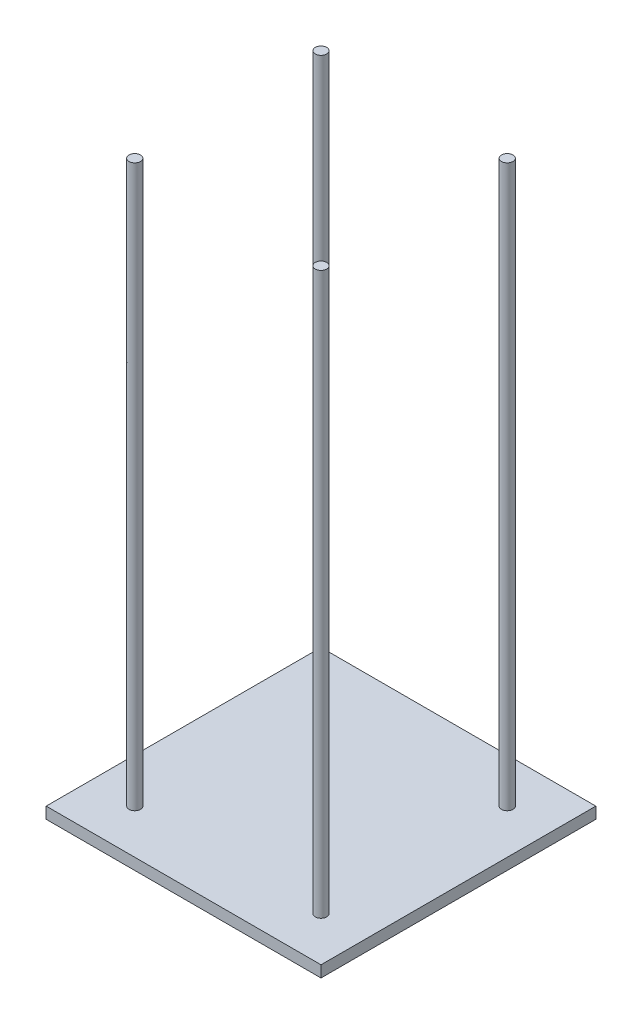
SolidWorks part; units mm, degrees
ref_plane "Front Plane" through (0, 0, 0) normal (0, 0, 1) x (1, 0, 0)
ref_plane "Top Plane" through (0, 0, 0) normal (0, 1, 0) x (1, 0, 0)
ref_plane "Right Plane" through (0, 0, 0) normal (1, 0, 0) x (0, 0, -1)
sketch "Sketch1" plane through (0, 0, 0) normal (0, 1, 0) x (1, 0, 0)
  line L0 (0, -60) -> (0, 60) construction
  line L1 (-60, 60) -> (60, 60)
  line L2 (-60, 60) -> (-60, -60)
  line L3 (-60, -60) -> (60, -60)
  line L4 (60, 60) -> (60, -60)
  line L5 (-60, 60) -> (60, -60) construction
  line L6 (-60, -60) -> (60, 60) construction
  line L7 (60, 0) -> (-60, 0) construction
  circle A0 centre (-40.6586, 40.6586) radius 2.5
  circle A1 centre (40.6586, -40.6586) radius 2.5
  circle A2 centre (40.6586, 40.6586) radius 2.5
  circle A3 centre (-40.6586, -40.6586) radius 2.5
  point P0 (0, 0)
  point P14 (44.8368, -35.9988)
  point P17 (0, 0)
  point P20 (0, 0)
  point P21 (-39.5068, 41.7787)
  point P22 (0, 0)
  point P23 (-40.6586, 40.6586)
  point P24 (-56.33, 56.33)
  dimension "D3" = 5
  dimension "D1" = 115
  dimension "D2" = 45
  dimension "D4" = 120
extrude "Boss-Extrude1" add sketch "Sketch1" along normal blind 5 contours L4 L1 L2 L3 A3 A2 A1 A0 region at (0, 0, 0)
extrude "Boss-Extrude2" add sketch "Sketch1<3>" along normal blind 250 contours A3 | A0 | A2 | A1 region at (-40.6586, 0, -40.6586) region at (40.6586, 0, 40.6586) region at (40.6586, 0, -40.6586) region at (-40.6586, 0, 40.6586)
sketch "Sketch1<3>" plane through (0, 0, 0) normal (0, 1, 0) x (1, 0, 0) same geometry as "Sketch1"
